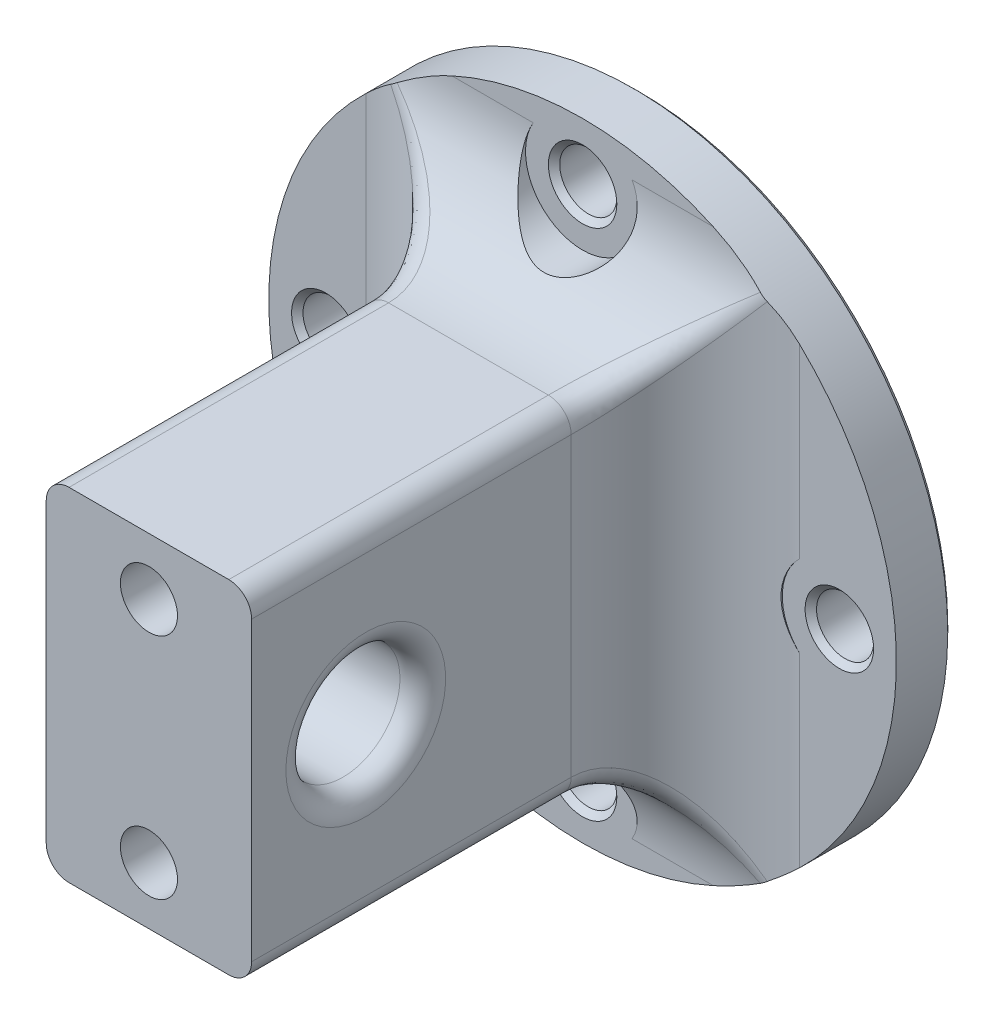
SolidWorks part; units mm, degrees
ref_plane "Front Plane" through (0, 0, 0) normal (0, 0, 1) x (1, 0, 0)
ref_plane "Top Plane" through (0, 0, 0) normal (0, 1, 0) x (1, 0, 0)
ref_plane "Right Plane" through (0, 0, 0) normal (1, 0, 0) x (0, 0, -1)
sketch "Sketch1" plane through (0, 0, 0) normal (0, 0, 1) x (1, 0, 0)
  circle A0 centre (0, 0) radius 27.5
  circle A1 centre (0, 22.5) radius 2.5
  circle A2 centre (0, -22.5) radius 2.5
  circle A3 centre (22.5, 0) radius 2.5
  circle A4 centre (-22.5, 0) radius 2.5
  circle A5 centre (0, 0) radius 22.5 construction
  dimension "D1" = 55
  dimension "D2" = 45
  dimension "D3" = 5
extrude "Boss-Extrude1" add sketch "Sketch1" along normal blind 5
sketch "Sketch2" plane through (0, 0, 5) normal (0, 0, 1) x (1, 0, 0)
  line L1 (-9, -15) -> (9, -15)
  line L2 (-9, -15) -> (-9, 15)
  line L3 (-9, 15) -> (9, 15)
  line L4 (9, -15) -> (9, 15)
  line L5 (-9, -15) -> (9, 15) construction
  line L6 (-9, 15) -> (9, -15) construction
  circle A0 centre (0, 10) radius 2.5
  circle A1 centre (0, -10) radius 2.5
  point P0 (0, 0)
  dimension "D1" = 5
  dimension "D2" = 10
  dimension "D3" = 10
  dimension "D4" = 30
  dimension "D5" = 18
extrude "Boss-Extrude2" add sketch "Sketch2" along normal blind 38
sketch "Sketch3" plane through (0, 0, 0) normal (0, 0, -1) x (-1, 0, 0)
  circle A0 centre (0, 10) radius 2.5 construction
  circle A1 centre (0, 10) radius 2.5 construction
  circle A2 centre (0, -10) radius 2.5 construction
  circle A3 centre (0, -10) radius 2.5 construction
  circle A4 centre (0, 10) radius 4.375
  circle A5 centre (0, -10) radius 4.375
  dimension "D1" = 8.75
extrude "Cut-Extrude1" cut sketch "Sketch3" against normal offset from surface (20 mm away) 8 from offset 15 up to face at (0, 0, 43) offset against normal yes
fillet "Fillet1" radius 10 4 edges at (0, 15, 5) (-9, 0, 5) (0, -15, 5) (9, 0, 5)
sketch "Sketch4" plane through (0, 0, 5) normal (0, 0, 1) x (1, 0, 0)
  circle A0 centre (0, 22.5) radius 2.5 construction
  circle A1 centre (0, 22.5) radius 2.5 construction
  circle A2 centre (0, -22.5) radius 2.5 construction
  circle A3 centre (0, -22.5) radius 2.5 construction
  circle A4 centre (0, 22.5) radius 5
  circle A5 centre (0, -22.5) radius 5
  circle A6 centre (-22.5, 0) radius 2.5 construction
  circle A7 centre (-22.5, 0) radius 2.5 construction
  circle A8 centre (22.5, 0) radius 2.5 construction
  circle A9 centre (22.5, 0) radius 2.5 construction
  circle A10 centre (-22.5, 0) radius 5
  circle A11 centre (22.5, 0) radius 5
  dimension "D1" = 10
extrude "Cut-Extrude2" cut sketch "Sketch4" along normal through all
chamfer "Chamfer1" distance 0.5 angle 45 9 edges at (-20, 0, 0) (25, 0, 0) (2.5, -22.5, 0) (2.5, 22.5, 0) (27.5, 0, 0) (-20, 0, 5) (2.5, -22.5, 5) (2.5, 22.5, 5) (25, 0, 5)
chamfer "Chamfer2" distance 2 angle 45 2 edges at (-4.375, 10, 35) (-4.375, -10, 35)
sketch "Sketch7" plane through (9, 0, 0) normal (1, 0, 0) x (0, 0, -1)
  line L7 (-43, -15) -> (-43, 15) construction
  circle A0 centre (-33, 0) radius 5
  point P2 (0, 0)
  dimension "D2" = 10
  dimension "D1" = 10
extrude "Cut-Extrude4" cut sketch "Sketch7" against normal through all
fillet "Fillet4" radius 2 8 edges at (-11.0039, -17.0039, 8.9947) (11.0039, -17.0039, 8.9947) (-11.0039, 17.0039, 8.9947) (11.0039, 17.0039, 8.9947) (-9, -15, 29) (9, -15, 29) (-9, 15, 29) (9, 15, 29)
sketch "Sketch8" plane through (-9, 0, 0) normal (-1, 0, 0) x (0, 0, 1)
  line L0 (21, -17.2533) -> (21, 18.8495) construction
  line L1 (43, 13) -> (43, -13) construction
  line L2 (24.25, 1.75) -> (25.75, 1.75)
  line L3 (24.25, 1.75) -> (24.25, -1.75)
  line L4 (24.25, -1.75) -> (25.75, -1.75)
  line L5 (25.75, 1.75) -> (25.75, -1.75)
  line L6 (24.25, 1.75) -> (25.75, -1.75) construction
  line L7 (24.25, -1.75) -> (25.75, 1.75) construction
  point P3 (25, 0)
  point P9 (0, 0)
  dimension "D1" = 1.5
  dimension "D2" = 3.5
  dimension "D3" = 4
  dimension "D4" = 22
fillet "Fillet5" radius 2 2 edges at (-9, 0, 28) (9, 0, 28)
ref_plane "Plane1" through (0, 0, 15) normal (0, 0, 1) x (1, 0, 0)
split "Split1" trim tools "Plane1" bodies to split 107 resulting bodies 110 111
